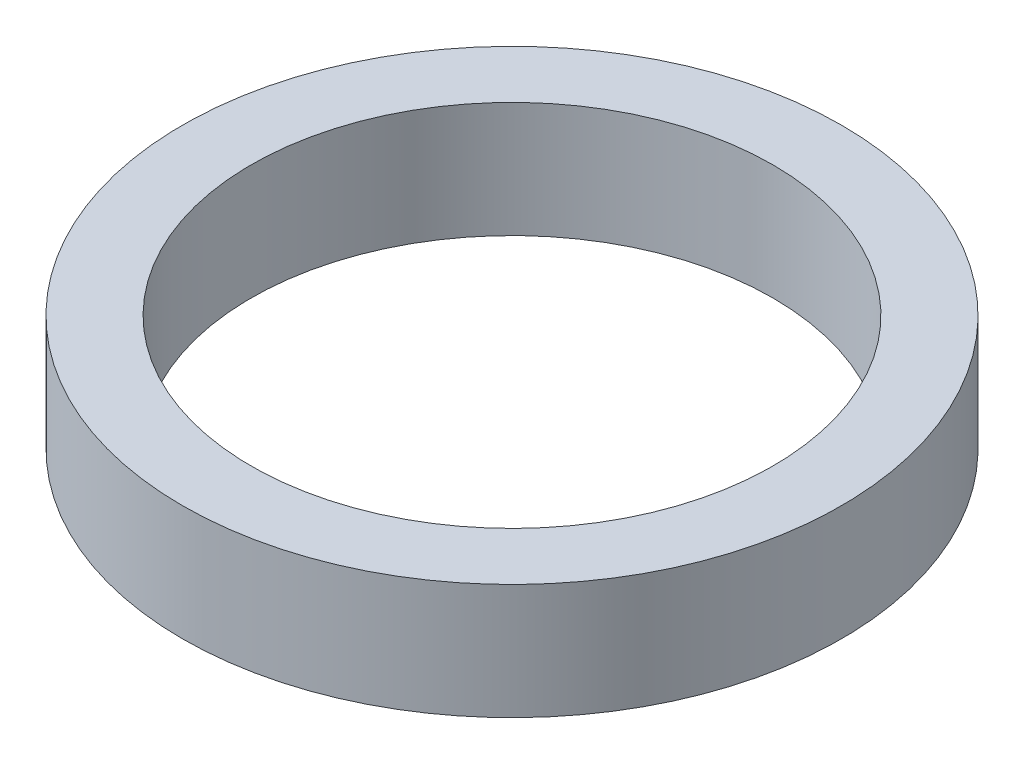
SolidWorks part; units mm, degrees
ref_plane "Front Plane" through (0, 0, 0) normal (0, 0, 1) x (1, 0, 0)
ref_plane "Top Plane" through (0, 0, 0) normal (0, 1, 0) x (1, 0, 0)
ref_plane "Right Plane" through (0, 0, 0) normal (1, 0, 0) x (0, 0, -1)
sketch "Sketch1" plane through (0, 0, 0) normal (0, 1, 0) x (1, 0, 0)
  circle A0 centre (0, 0) radius 60
  dimension "FLANGE_OD" = 120
extrude "Boss-Extrude1" add sketch "Sketch1" along normal blind 21
sketch "Sketch2" plane through (0, 0, 0) normal (0, 1, 0) x (1, 0, 0)
  circle A0 centre (0, 0) radius 47.5
  dimension "BORE_D" = 95
extrude "Cut-Extrude1" cut sketch "Sketch2" along normal through all
sketch "Sketch3" plane through (0, 21, 0) normal (0, 1, 0) x (1, 0, 0)
  circle A0 centre (0, 0) radius 26.6049 construction
  circle A1 centre (-26.6049, 0) radius 1.6674
  dimension "BOLT_D" = 3.3348
  dimension "BOLT_PCD" = 53.2099
extrude "Cut-Extrude2" cut sketch "Sketch3" against normal blind 17.9412 rebuild error yes
pattern_circular "CirPattern1" count 8 over 360 rebuild error yes
